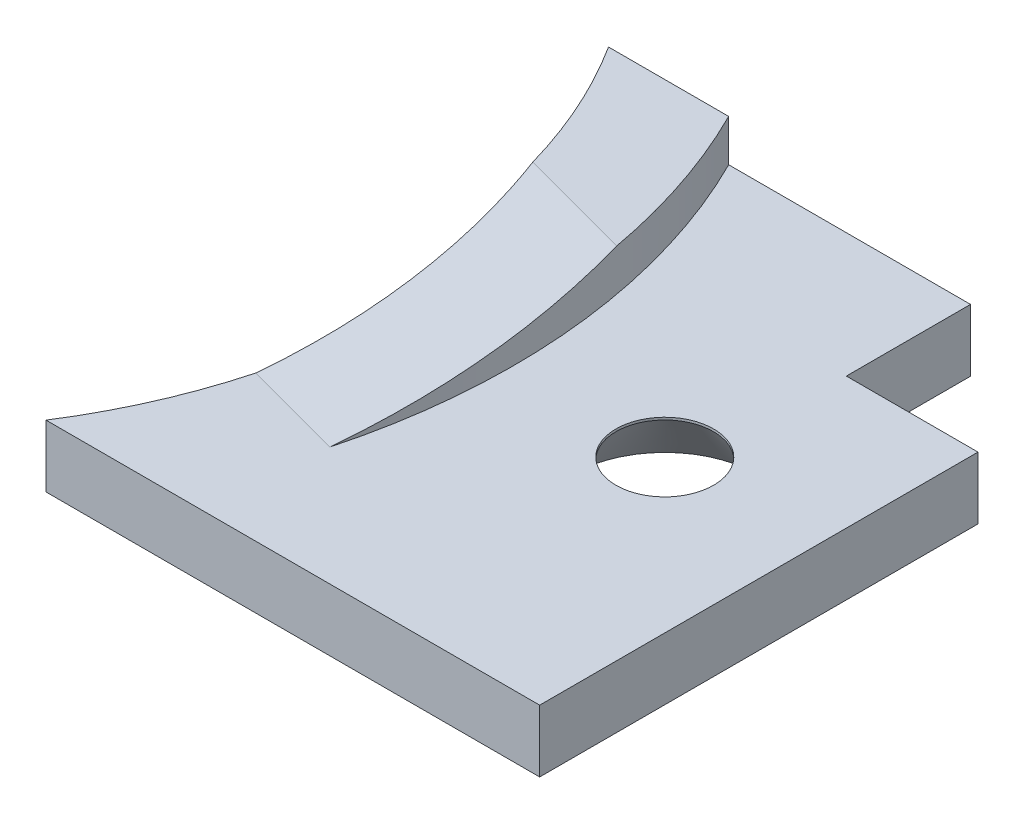
SolidWorks part; units mm, degrees
ref_plane "Front Plane" through (0, 0, 0) normal (0, 0, 1) x (1, 0, 0)
ref_plane "Top Plane" through (0, 0, 0) normal (0, 1, 0) x (1, 0, 0)
ref_plane "Right Plane" through (0, 0, 0) normal (1, 0, 0) x (0, 0, -1)
sketch "Sketch1" plane through (0, 0, 0) normal (0, 1, 0) x (1, 0, 0)
  line L0 (-4.4, 18.8) -> (-4.4, 14.65)
  line L1 (-16.5, 18.8) -> (0, 18.8)
  line L3 (-16.5, 0) -> (0, 0)
  line L4 (0, 18.8) -> (0, 0)
  line L5 (-4.4, 14.65) -> (0, 14.65)
  circle A0 centre (-5.09, 9.271) radius 1.632
  arc A10 (-16.5, 0) -> (-16.5, 18.8) centre (-31.2611, 9.4) ccw
  dimension "D11" = 17.5
  dimension "D2" = 3.264
  dimension "D1" = 18.8
  dimension "D3" = 16.5
  dimension "D7" = 4.4
  dimension "D8" = 4.15
  dimension "D10" = 5.09
  dimension "D13" = 9.271
  dimension "D14" = 9.529
extrude "Boss-Extrude1" add sketch "Sketch1" along normal blind 2.08 contours A10 L3 L4 L5 L0 L1 A0 region at (-7.7975, 0, -8.8665)
sketch "Sketch2" plane through (0, 2.08, 0) normal (0, 1, 0) x (1, 0, 0)
  line L0 (-16.5, 18.8) -> (-12.4824, 18.8)
  line L1 (-16.5, 18.8) -> (-4.4, 18.8) construction
  line L2 (-31.2611, 9.4) -> (-10.9767, 3.9648)
  line L3 (-16.5, 0) -> (-12.4824, 0)
  line L4 (-31.2611, 9.4) -> (-10.2611, 9.4) construction
  arc A0 (-12.4824, 0) -> (-12.4824, 18.8) centre (-31.2611, 9.4) ccw
  arc A1 (-16.5, 0) -> (-16.5, 18.8) centre (-31.2611, 9.4) ccw construction
  arc A2 (-16.5, 0) -> (-16.5, 18.8) centre (-31.2611, 9.4) ccw
  arc M3 (-16.5, 18.8) -> (-16.5, 0) centre (-31.2611, 9.4) cw
  line M8 (-4.4, 18.8) -> (-16.5, 18.8)
  dimension "D1" = 3.5
  dimension "D2" = 15
extrude "Boss-Extrude2" add sketch "Sketch2" along normal blind 1.4 contours L2 A0 M8 M3 | L4 A2 L2 A0 region at (-12.8441, 2.08, -14.2059) region at (-12.1778, 2.08, -6.8876)
chamfer "Chamfer1" distance 1.4 distance2 9 1 edges at (-12.667, 3.48, -4.4177) first distance on face at (-12.667, 2.78, -4.4177)
chamfer "Chamfer2" distance 2 distance2 1.5 1 edges at (-5.09, 0, -7.639) first distance on face at (-5.09, 2.08, -7.639)
